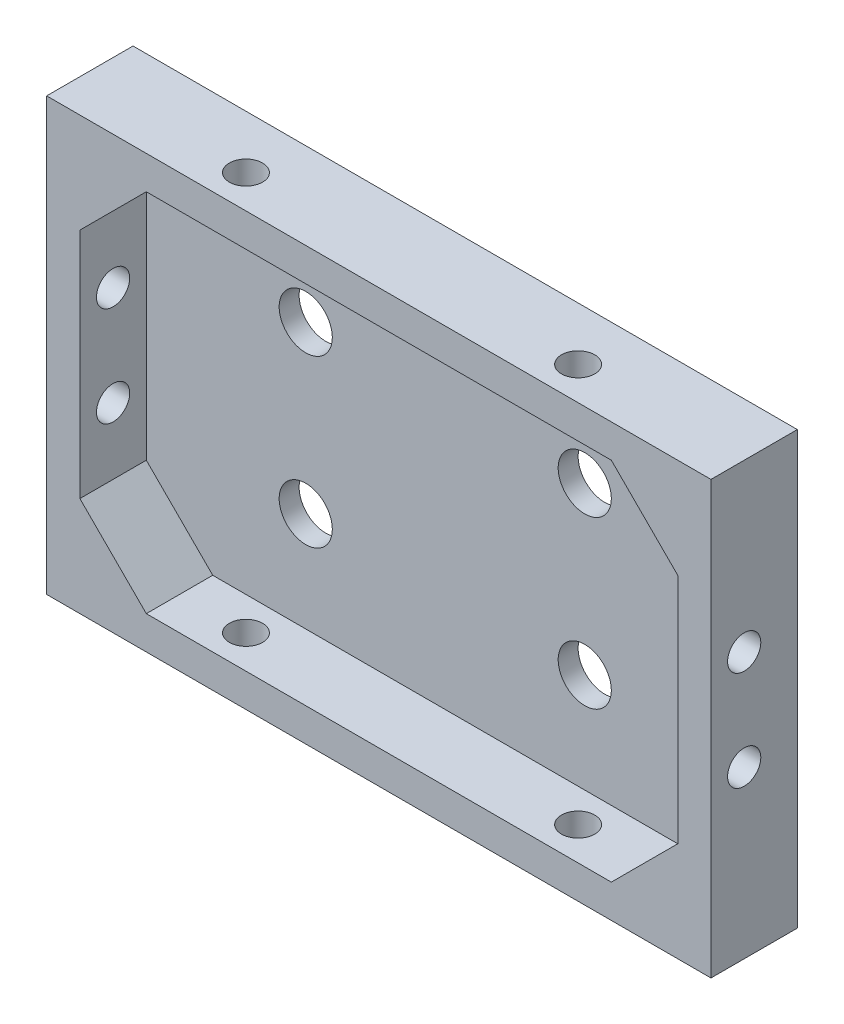
SolidWorks part; units mm, degrees
ref_plane "Plan de face" through (0, 0, 0) normal (0, 0, 1) x (1, 0, 0)
ref_plane "Plan de dessus" through (0, 0, 0) normal (0, 1, 0) x (1, 0, 0)
ref_plane "Plan de droite" through (0, 0, 0) normal (1, 0, 0) x (0, 0, -1)
sketch "Esquisse1" plane through (0, 0, 0) normal (0, 0, 1) x (1, 0, 0)
  line L0 (44.1184, 33.7284) -> (54.1184, 33.7284)
  line L1 (-45.8816, 33.7284) -> (44.1184, 33.7284)
  line L2 (-45.8816, 33.7284) -> (-45.8816, -31.2716)
  line L3 (-45.8816, -31.2716) -> (54.1184, -31.2716)
  line L4 (54.1184, 23.7284) -> (54.1184, -31.2716)
  line L5 (54.1184, 33.7284) -> (54.1184, 23.7284)
  point P6 (54.1184, 33.7284)
  dimension "D1" = 100
  dimension "D2" = 65
extrude "Boss.-Extru.1" add sketch "Esquisse1" along normal blind 13
shell "Coque1" thickness 5 removed face at (4.1184, 1.2284, 13)
sketch "Esquisse2" plane through (-45.8816, 0, 0) normal (-1, 0, 0) x (0, 0, 1)
  line L0 (13, 33.7284) -> (13, -31.2716) construction
  line L1 (13, 33.7284) -> (0, 33.7284) construction
  line L2 (13, -31.2716) -> (0, -31.2716) construction
  circle A0 centre (8, 8.7284) radius 2.5
  circle A1 centre (8, -6.2716) radius 2.5
  dimension "D1" = 5
  dimension "D2" = 5
  dimension "D3" = 5
  dimension "D4" = 5
  dimension "D5" = 25
  dimension "D6" = 25
extrude "Enlèv. mat.-Extru.1" cut sketch "Esquisse2" against normal up to surface (100 mm away) contours A1 | A0 region at (-45.8816, -6.2716, 8) up to face at (54.1184, 1.2284, 6.5)
sketch "Esquisse3" plane through (0, -31.2716, 0) normal (0, -1, 0) x (1, 0, 0)
  line L0 (-45.8816, 13) -> (54.1184, 13) construction
  line L2 (54.1184, 13) -> (54.1184, 0) construction
  line L3 (-45.8816, 13) -> (-45.8816, 0) construction
  circle A0 centre (-20.8816, 8) radius 2.5
  circle A1 centre (29.1184, 8) radius 2.5
  dimension "D1" = 5
  dimension "D2" = 5
  dimension "D3" = 5
  dimension "D4" = 5
  dimension "D5" = 25
  dimension "D6" = 25
extrude "Enlèv. mat.-Extru.2" cut sketch "Esquisse3" against normal up to surface (65 mm away) up to face at (4.1184, 33.7284, 6.5)
sketch "Esquisse4" plane through (0, 0, 3) normal (0, 0, 1) x (1, 0, 0)
  line L0 (-30.8816, 28.7284) -> (-40.8816, 18.7284)
  line L1 (49.1184, 28.7284) -> (-40.8816, 28.7284) construction
  line L2 (-40.8816, 28.7284) -> (-40.8816, -26.2716) construction
  line L3 (-40.8816, 18.7284) -> (-40.8816, 28.7284)
  line L4 (-40.8816, 28.7284) -> (-30.8816, 28.7284)
  line L5 (49.1184, 28.7284) -> (49.1184, 18.7284)
  line L6 (49.1184, -26.2716) -> (49.1184, 28.7284) construction
  line L7 (49.1184, 18.7284) -> (39.1184, 28.7284)
  line L8 (39.1184, 28.7284) -> (49.1184, 28.7284)
  line L9 (49.1184, 28.7284) -> (-40.8816, 28.7284) construction
  line L10 (49.1184, -26.2716) -> (49.1184, -16.2716)
  line L11 (49.1184, -16.2716) -> (39.1184, -26.2716)
  line L12 (-40.8816, -26.2716) -> (49.1184, -26.2716) construction
  line L13 (39.1184, -26.2716) -> (49.1184, -26.2716)
  line L14 (-30.8816, -26.2716) -> (-40.8816, -16.2716)
  line L15 (-40.8816, 28.7284) -> (-40.8816, -26.2716) construction
  line L16 (-40.8816, -16.2716) -> (-40.8816, -26.2716)
  line L17 (-40.8816, -26.2716) -> (-30.8816, -26.2716)
  dimension "D1" = 10
  dimension "D2" = 10
  dimension "D3" = 10
  dimension "D4" = 10
  dimension "D5" = 10
  dimension "D6" = 10
  dimension "D7" = 10
  dimension "D8" = 10
extrude "Boss.-Extru.2" add sketch "Esquisse4" along normal up to surface (10 mm away) up to face at (4.1184, 1.2284, 13)
sketch "Esquisse5" plane through (0, 0, 3) normal (0, 0, 1) x (1, 0, 0)
  line L0 (54.1184, 33.7284) -> (-45.8816, 33.7284) construction
  line L2 (-45.8816, 33.7284) -> (-45.8816, -31.2716) construction
  circle A0 centre (-16.8816, 13.7284) radius 4
  dimension "D1" = 8
  dimension "D4" = 20
  dimension "D6" = 29
extrude "Enlèv. mat.-Extru.3" cut sketch "Esquisse5" against normal up to surface (3 mm away) up to face at (4.1184, 1.2284, 0)
pattern_linear "Répétition linéaire1" count 2 spacing 42 along (1, 0, 0) count 2 spacing 25 along (0, -1, 0) of "Enlèv. mat.-Extru.3"
